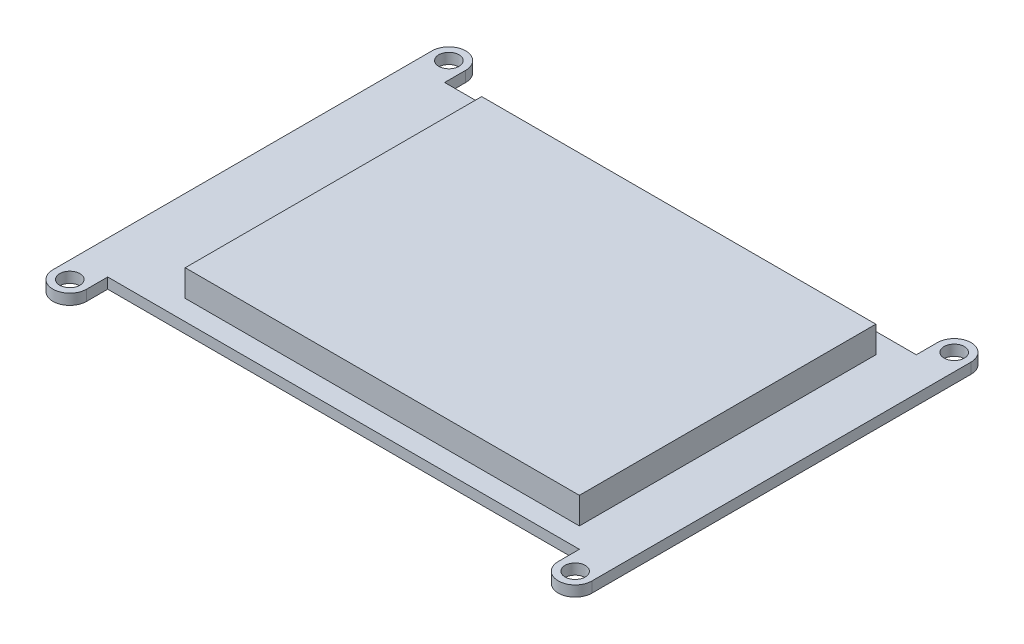
SolidWorks part; units mm, degrees
other "Markup3"
sketch "Sketch5" plane through (0, 4, 5.72) normal (-0.0867, 0.8312, 0.5491) x (0.8349, 0.3613, -0.4151)
ref_plane "Front Plane" through (0, 0, 0) normal (0, 0, 1) x (1, 0, 0)
ref_plane "Top Plane" through (0, 0, 0) normal (0, 1, 0) x (1, 0, 0)
ref_plane "Right Plane" through (0, 0, 0) normal (1, 0, 0) x (0, 0, -1)
sketch "Sketch1" plane through (0, 0, 0) normal (0, 1, 0) x (1, 0, 0)
  line L0 (76.2, 50.8) -> (76.2, 53.98)
  line L1 (0, 0) -> (81.28, 0)
  line L2 (0, 0) -> (0, 50.8)
  line L3 (0, 50.8) -> (81.28, 50.8)
  line L4 (81.28, 0) -> (81.28, 50.8)
  line L5 (81.28, 0) -> (81.28, -3.18)
  line L6 (0, 0) -> (0, -3.18)
  line L7 (5.08, 0) -> (5.08, -3.18)
  line L8 (76.2, 0) -> (76.2, -3.18)
  line L9 (0, 50.8) -> (0, 53.98)
  line L10 (5.08, 50.8) -> (5.08, 53.98)
  line L11 (81.28, 50.8) -> (81.28, 53.98)
  line L13 (13.716, 47.752) -> (73.152, 47.752)
  line L14 (13.716, 47.752) -> (13.716, 3.048)
  line L15 (13.716, 3.048) -> (73.152, 3.048)
  line L16 (73.152, 47.752) -> (73.152, 3.048)
  line L17 (66.167, 50.8) -> (54.737, 50.8)
  line L18 (66.167, 50.8) -> (66.167, 33.8)
  line L19 (66.167, 33.8) -> (54.737, 33.8)
  line L20 (54.737, 50.8) -> (54.737, 33.8)
  circle A0 centre (2.54, 53.98) radius 1.524
  arc A1 (0, 53.98) -> (5.08, 53.98) centre (2.54, 53.98) cw
  arc A2 (0, -3.18) -> (5.08, -3.18) centre (2.54, -3.18) ccw
  circle A3 centre (2.54, -3.18) radius 1.524
  circle A4 centre (78.74, 53.98) radius 1.524
  circle A5 centre (78.74, -3.18) radius 1.524
  arc A6 (76.2, 53.98) -> (81.28, 53.98) centre (78.74, 53.98) cw
  arc A7 (76.2, -3.18) -> (81.28, -3.18) centre (78.74, -3.18) ccw
  point P35 (60.452, 33.8)
  dimension "D6" = 3.048
  dimension "D1" = 81.28
  dimension "D2" = 50.8
  dimension "D3" = 3.18
  dimension "D4" = 3.18
  dimension "D5" = 5.08
  dimension "D7" = 3.18
  dimension "D8" = 5.08
  dimension "D9" = 3.18
  dimension "D10" = 3.048
  dimension "D11" = 13.716
  dimension "D12" = 59.436
  dimension "D13" = 20.828
  dimension "D14" = 11.43
  dimension "D15" = 17
extrude "Y+ PCB extr" add sketch "Sketch1" along normal blind 1.6 contours L1 L4 L3 L2 region at (78.74, 0, -49.8415)
extrude "Z0X0 corner extr" add sketch "Sketch1<5>" along normal blind 1.6 contours A1 L9 L3 L10 A0 region at (2.54, 0, -50.8765)
sketch "Sketch1<5>" plane through (0, 0, 0) normal (0, 1, 0) x (1, 0, 0) same geometry as "Sketch1"
extrude "Z0X+ corner extr" add sketch "Sketch1<6>" along normal blind 1.6 contours A6 L0 L3 L11 A4 region at (76.2765, 0, -52.39)
sketch "Sketch1<6>" plane through (0, 0, 0) normal (0, 1, 0) x (1, 0, 0) same geometry as "Sketch1"
extrude "Z+X0 corner extr" add sketch "Sketch1<7>" along normal blind 1.6 contours L6 A2 L7 L1 A3 region at (5.0035, 0, 1.59)
sketch "Sketch1<7>" plane through (0, 0, 0) normal (0, 1, 0) x (1, 0, 0) same geometry as "Sketch1"
extrude "Z+X+ corner extr" add sketch "Sketch1<8>" along normal blind 1.6 contours L8 A7 L5 L1 A5 region at (81.2035, 0, 1.59)
sketch "Sketch1<8>" plane through (0, 0, 0) normal (0, 1, 0) x (1, 0, 0) same geometry as "Sketch1"
extrude "Y+ display extr" add sketch "Sketch1<10>" along normal blind 5.6 contours L16 L13 L14 L15 region at (42.3474, 0, -24.4182)
sketch "Sketch1<10>" plane through (0, 0, 0) normal (0, 1, 0) x (1, 0, 0) same geometry as "Sketch1"
extrude "Y+ display extr behind uSD" add sketch "Sketch1<11>" along normal blind 5.6 contours L13 L20 L19 L18 region at (60.452, 0, -40.776)
sketch "Sketch1<11>" plane through (0, 0, 0) normal (0, 1, 0) x (1, 0, 0) same geometry as "Sketch1"
extrude "Y- uSD extr outer edge" add sketch "Sketch1<12>" along normal blind 1.6 contours L3 L20 L13 L18 region at (60.452, 0, -49.276)
sketch "Sketch1<12>" plane through (0, 0, 0) normal (0, 1, 0) x (1, 0, 0) same geometry as "Sketch1"
extrude "Y- uSD extr" add sketch "Sketch1<13>" against normal blind 2 contours L13 L20 L19 L18 region at (60.452, 0, -40.776)
sketch "Sketch1<13>" plane through (0, 0, 0) normal (0, 1, 0) x (1, 0, 0) same geometry as "Sketch1"
extrude "Y- uSD extr outer bottom" add sketch "Sketch1<14>" against normal blind 2 contours L3 L20 L13 L18 region at (60.452, 0, -49.276)
sketch "Sketch1<14>" plane through (0, 0, 0) normal (0, 1, 0) x (1, 0, 0) same geometry as "Sketch1"
